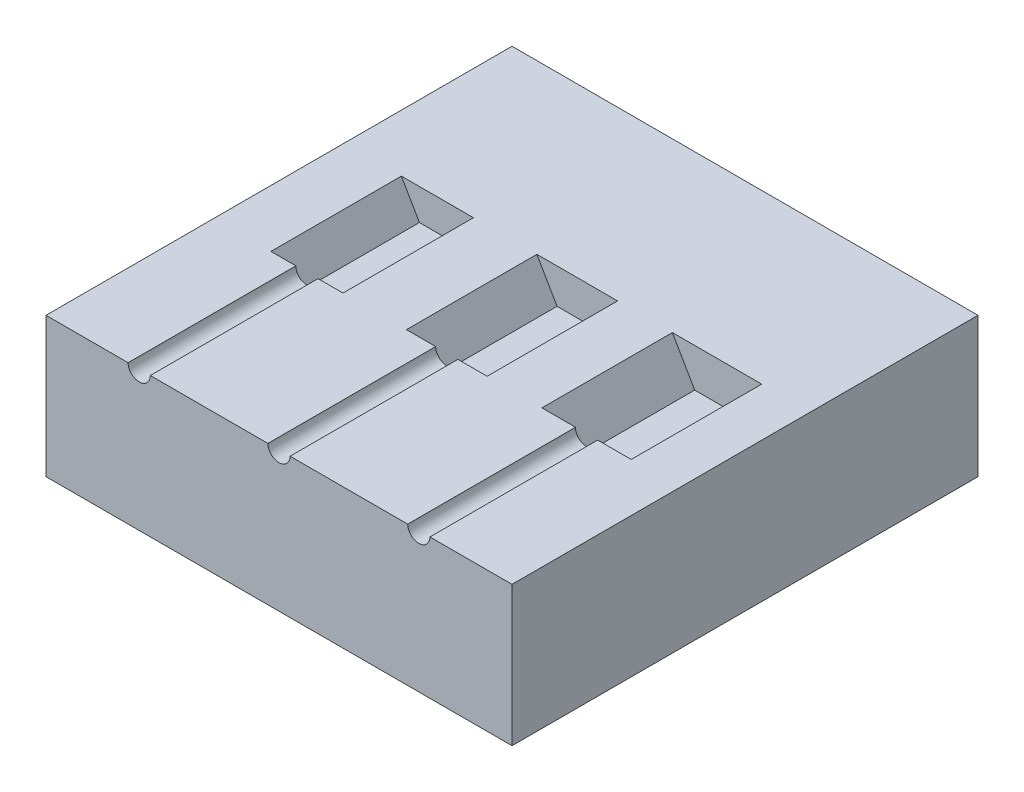
SolidWorks part; units mm, degrees
ref_plane "Front Plane" through (0, 0, 0) normal (0, 0, 1) x (1, 0, 0)
ref_plane "Top Plane" through (0, 0, 0) normal (0, 1, 0) x (1, 0, 0)
ref_plane "Right Plane" through (0, 0, 0) normal (1, 0, 0) x (0, 0, -1)
sketch "Sketch2" plane through (0, 0, 0) normal (0, 1, 0) x (1, 0, 0)
  line L1 (0, 0) -> (25, 0)
  line L2 (0, 0) -> (0, 25)
  line L3 (0, 25) -> (25, 25)
  line L4 (25, 0) -> (25, 25)
  dimension "D1" = 25
  dimension "D2" = 25
extrude "Boss-Extrude1" add sketch "Sketch2" along normal blind 7.5
ref_plane "Plane1" through (0, 0, -12.5) normal (0, 0, 1) x (1, 0, 0)
sketch "Sketch3" plane through (0, 0, -12.5) normal (0, 0, 1) x (1, 0, 0)
  line L0 (4.0329, 5.825) -> (5.9671, 5.825)
  line L1 (5.9671, 5.825) -> (6.9341, 7.5)
  line L2 (0, 7.5) -> (25, 7.5) construction
  line L3 (6.9341, 7.5) -> (3.0659, 7.5)
  line L4 (5, 7.5) -> (5, 0) construction
  line L6 (4.0329, 5.825) -> (3.0659, 7.5)
  line L7 (11.4175, 5.625) -> (13.5825, 5.625)
  line L8 (13.5825, 5.625) -> (14.6651, 7.5)
  line L9 (14.6651, 7.5) -> (10.3349, 7.5)
  line L10 (12.5, 7.5) -> (12.5, 0) construction
  line L11 (11.4175, 5.625) -> (10.3349, 7.5)
  line L12 (0, 0) -> (25, 0) construction
  line L13 (18.802, 5.425) -> (21.198, 5.425)
  line L14 (21.198, 5.425) -> (22.396, 7.5)
  line L15 (22.396, 7.5) -> (17.604, 7.5)
  line L16 (20, 7.5) -> (20, 0) construction
  line L17 (18.802, 5.425) -> (17.604, 7.5)
  line L18 (0, 7.5) -> (0, 0) construction
  line L19 (25, 7.5) -> (25, 0) construction
  point P0 (18.2957, 7.5)
  point P11 (5, 5.825)
  point P16 (12.5, 5.625)
  point P25 (20, 5.425)
  dimension "D1" = 120
  dimension "D2" = 1.675
  dimension "D3" = 120
  dimension "D4" = 1.875
  dimension "D5" = 120
  dimension "D6" = 2.075
  dimension "D7" = 5
  dimension "D8" = 5
extrude "Cut-Hex" cut sketch "Sketch3" against normal blind 3.5 and the other way blind 3.5
sketch "Sketch4" plane through (0, 0, -9) normal (0, 0, -1) x (-1, 0, 0)
  line L0 (-25, 7.5) -> (0, 7.5) construction
  line L1 (-22.396, 7.5) -> (-17.604, 7.5) construction
  line L2 (-6.9341, 7.5) -> (-3.0659, 7.5) construction
  circle A0 centre (-12.5, 7.5) radius 0.5955
  circle A1 centre (-20, 7.5) radius 0.5955
  circle A2 centre (-5, 7.5) radius 0.5955
  dimension "D1" = 1.191
extrude "Cut-Cable Exit" cut sketch "Sketch4" against normal through all
